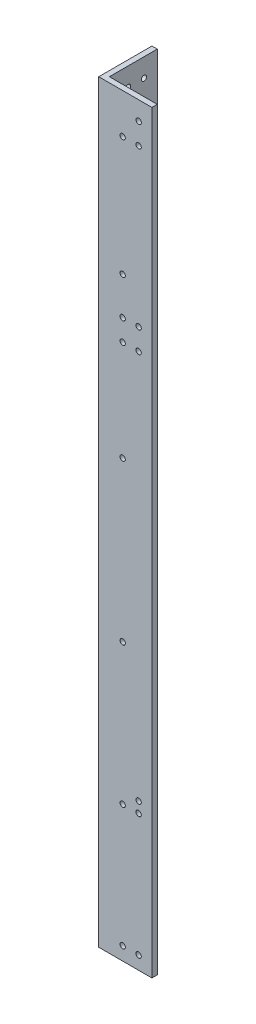
SolidWorks part; units mm, degrees
ref_plane "Front Plane" through (0, 0, 0) normal (0, 0, 1) x (1, 0, 0)
ref_plane "Top Plane" through (0, 0, 0) normal (0, 1, 0) x (1, 0, 0)
ref_plane "Right Plane" through (0, 0, 0) normal (1, 0, 0) x (0, 0, -1)
sketch "Sketch2" plane through (0, 0, 0) normal (0, 1, 0) x (1, 0, 0)
  line L0 (0, 31.75) -> (3.175, 31.75)
  line L1 (3.175, 31.75) -> (3.175, 3.175)
  line L2 (3.175, 3.175) -> (31.75, 3.175)
  line L3 (31.75, 3.175) -> (31.75, 0)
  line L4 (31.75, 0) -> (0, 0)
  line L5 (0, 0) -> (0, 31.75)
  point P9 (1.5875, 31.75)
  point P10 (31.75, 1.5875)
  dimension "D4" = 3.175
  dimension "D1" = 31.75
  dimension "D2" = 31.75
  dimension "D3" = 3.175
extrude "Boss-Extrude1" add sketch "Sketch2" along normal blind 450
sketch "LeftSideHoles-Sketch3" plane through (0, 0, 0) normal (0, 0, 1) x (1, 0, 0)
  line L0 (0, 0) -> (31.75, 0) construction
  line L1 (0, 450) -> (31.75, 450) construction
  line L3 (0, 450) -> (0, 0) construction
  circle A0 centre (14.2875, 81.1125) radius 1.5875
  circle A1 centre (23.8125, 81.1125) radius 1.5875
  circle A3 centre (23.8125, 87.4625) radius 1.5875
  circle A5 centre (14.2875, 426.1875) radius 1.5875
  circle A6 centre (23.8125, 438.8875) radius 1.5875
  circle A7 centre (23.8125, 426.1875) radius 1.5875
  circle A10 centre (14.2875, 332.6026) radius 1.5875
  circle A11 centre (23.8125, 332.6026) radius 1.5875
  circle A12 centre (14.2875, 319.9026) radius 1.5875
  circle A13 centre (23.8125, 319.9026) radius 1.5875
  circle A14 centre (14.2875, 7.9375) radius 1.5875
  circle A15 centre (23.8125, 7.9375) radius 1.5875
  circle A16 centre (14.2875, 165) radius 1.5875
  circle A17 centre (14.2875, 260) radius 1.5875
  circle A18 centre (14.2875, 355) radius 1.5875
  point P24 (15.875, 0)
  dimension "D4" = 3.175
  dimension "D1" = 81.1125
  dimension "D2" = 14.2875
  dimension "D10" = 7.9375
  dimension "D7" = 12.7
  dimension "D3" = 9.525
  dimension "D11" = 332.6026
  dimension "D12" = 165
  dimension "D13" = 95
  dimension "D14" = 95
  dimension "D5" = 6.35
  dimension "D6" = 12.7
  dimension "D8" = 11.1125
sketch "BackSideHoles-Sketch4" plane through (0, 0, 0) normal (-1, 0, 0) x (0, 0, 1)
  line L0 (-31.75, 450) -> (0, 450) construction
  line L2 (0, 450) -> (0, 0) construction
  line L3 (-31.75, 0) -> (0, 0) construction
  circle A0 centre (-23.8125, 81.1125) radius 1.5875
  circle A2 centre (-23.8125, 87.4625) radius 1.5875
  circle A3 centre (-14.2875, 87.4625) radius 1.5875
  circle A4 centre (-23.8125, 438.8875) radius 1.5875
  circle A5 centre (-14.2875, 438.8875) radius 1.5875
  circle A6 centre (-23.8125, 426.1875) radius 1.5875
  circle A10 centre (-23.8125, 332.6026) radius 1.5875
  circle A11 centre (-14.2875, 332.6026) radius 1.5875
  circle A12 centre (-23.8125, 326.2526) radius 1.5875
  circle A13 centre (-14.2875, 326.2526) radius 1.5875
  circle A14 centre (-14.2875, 165) radius 1.5875
  circle A15 centre (-14.2875, 260) radius 1.5875
  circle A16 centre (-14.2875, 355) radius 1.5875
  circle A17 centre (-23.8125, 7.9375) radius 1.5875
  circle A18 centre (-14.2875, 7.9375) radius 1.5875
  dimension "D4" = 3.175
  dimension "D2" = 14.2875
  dimension "D7" = 12.7
  dimension "D5" = 6.35
  dimension "D6" = 11.1125
  dimension "D8" = 6.35
  dimension "D1" = 332.6026
  dimension "D10" = 165
  dimension "D11" = 95
  dimension "D12" = 95
  dimension "D13" = 7.9375
  dimension "D3" = 81.1125
  dimension "D9" = 9.525
extrude "LeftSideHoles-Cut-Extrude1" cut sketch "LeftSideHoles-Sketch3" against normal blind 3.175
extrude "BackSideHoles-Cut-Extrude2" cut sketch "BackSideHoles-Sketch4" against normal blind 3.175
equation "\"RailThickness\"= .125in'Spec"
equation "\"VSWidth\"= 1.25in'Spec"
equation "\"VSHeight\"= 1.25in'Spec"
equation "\"VSLength\"= 450mm"
equation "\"HoleOffsetFromEdge\"= \"RailThickness\" * 2.5"
equation "\"HoleOffsetFromSide\"= \"RailThickness\" * 3.5"
equation "\"LegHeight\"= 70mm'Space needed for PSU/Stepper/Electronics"
equation "\"VSBottomSideRailHoleY1FromBottomOfLowerRail\"= \"V1 BottomOfLowerRail\" + \"HoleOffsetFromSide\"'Equals 70.1125"
equation "\"VSSideRailHoleX1FromSide\"= \"HoleOffsetFromSide\" + \"RailThickness\""
equation "\"FasteningHoleDiameter\"= .125in"
equation "\"VSBottomSideRailHoleY2FromY1\"= \"LowerRailHeight\" - \"HoleOffsetFromSide\" - \"HoleOffsetFromEdge\"'Equals 6.35"
equation "\"VSTopSideRailHoleY1FromEdge\"= \"HoleOffsetFromEdge\" + \"RailThickness\""
equation "\"D4@LeftSideHoles-Sketch3\"=\"FasteningHoleDiameter\""
equation "\"D1@LeftSideHoles-Sketch3\"=\"VSBottomSideRailHoleY1FromBottomOfLowerRail\""
equation "\"D2@LeftSideHoles-Sketch3\"=\"VSSideRailHoleX1FromSide\""
equation "\"D1@Boss-Extrude1\"=\"VSLength\""
equation "\"D4@BackSideHoles-Sketch4\" = \"FasteningHoleDiameter\""
equation "\"VSMidSideRailHoleY1FromV8TopOfMidSideRail\"= \"V8 ToTopOfMidSideRail\" - \"HoleOffsetFromEdge\"'Equals 308.2875"
equation "\"LowerRailHeight\"= 1.00in"
equation "\"D1@Sketch2\"=\"VSHeight\""
equation "\"D2@Sketch2\"=\"VSWidth\""
equation "\"MidBackRailHeight\"= 1.00in"
equation "\"VSMidBackRailHoleY1FromV7TopOfMidBackRail\"= \"V7 ToTopOfMidBackRail\" - \"HoleOffsetFromSide\"'Equals 308.2875"
equation "\"TopRailHeight\"= 1.25in"
equation "\"MidSideRailHeight\"= 1.25in"
equation "\"D10@LeftSideHoles-Sketch3\"=\"HoleOffsetFromEdge\""
equation "\"VSMidBackRailHoleY2FromY1\"= \"MidBackRailHeight\" - \"HoleOffsetFromSide\" - \"HoleOffsetFromEdge\"'Equals 6.35"
equation "\"VSMidSideRailHoleY2FromY1\"= \"MidSideRailHeight\" - \"HoleOffsetFromSide\" - \"HoleOffsetFromEdge\"'Equals 12.7"
equation "\"D7@LeftSideHoles-Sketch3\"=\"VSMidSideRailHoleY2FromY1\""
equation "\"D8@BackSideHoles-Sketch4\"=\"VSMidBackRailHoleY2FromY1\""
equation "\"D6@BackSideHoles-Sketch4\"=\"VSTopSideRailHoleY1FromEdge\""
equation "\"VSTopSideRailHoleY2FromY1\"= \"TopRailHeight\" - \"VSTopSideRailHoleY1FromEdge\" - \"HoleOffsetFromEdge\"'Equals 12.7"
equation "\"D7@BackSideHoles-Sketch4\"=\"VSTopSideRailHoleY2FromY1\""
equation "\"VSBottomSideRailHoleX2FromX1\"= \"VSWidth\" - \"VSSideRailHoleX1FromSide\" - \"HoleOffsetFromEdge\""
equation "\"D3@LeftSideHoles-Sketch3\"=\"VSBottomSideRailHoleX2FromX1\""
equation "\"V1 BottomOfLowerRail\"= \"LegHeight\""
equation "\"StepperShaftLength\"= 24mm'Pulley will be attached to the end"
equation "\"ZAxisLeadScrewLength\"= 200mm"
equation "\"LM8UUHeight\"= 24mm'Spec"
equation "\"V2 ToBedAtTopOfZAxis\"= \"V1 BottomOfLowerRail\" + \"StepperShaftLength\" + \"ZAxisLeadScrewLength\" - \"LM8UUHeight\" / 2"
equation "\"HotEndToTopOfXAxisGB\"= 63.315144mm'Measured from the100.Should be 63.315144"
equation "\"TopOfGBToBottomOfLinearRail\"= \"LinearGBWidth\" / 2 + \"LinearRailWidth\" / 2"
equation "\"LinearGBWidth\"= 27mm'Spec"
equation "\"V5 ToBottomOfXAxisLinearRail\"= \"V4 ToTopOfBuildPlate/HotEndTip\" + \"HotEndToTopOfXAxisGB\" - \"TopOfGBToBottomOfLinearRail\""
equation "\"LinearRailWidth\"= 12mm'Spec"
equation "\"V6 ToBottomOfGantryPulley\"= \"V5 ToBottomOfXAxisLinearRail\" - \"DistanceFromGABTopToLowerPulley\""
equation "\"GABUpperHeight\"= 6mm"
equation "\"GABMidWallHeight\"= 28mm'Must equal 28 or changes alignment"
equation "\"20TGT2PulleyWidth\"= 8.7mm'The STL of the Pulley in the diagram is a bit larger"
equation "\"GABMidShortRiserHeight\"= \"GABMidWallHeight\" / 2 - \"20TGT2PulleyWidth\"'Equals 5.3"
equation "\"GABRiserBossOffset\"= 0.8mm'Aligns Pulleys"
equation "\"DistanceFromGABTopToLowerPulley\"= \"GABUpperHeight\" + \"GABMidWallHeight\" - \"GABMidShortRiserHeight\" + \"GABRiserBossOffset\" / 2"
equation "\"V7 ToTopOfMidBackRail\"= \"V6 ToBottomOfGantryPulley\" + \"StepperShaftLength\""
equation "\"D1@BackSideHoles-Sketch4\" = \"VSMidBackRailHoleY1FromV7TopOfMidBackRail\""
equation "\"D11@LeftSideHoles-Sketch3\"=\"VSMidSideRailHoleY1FromV8TopOfMidSideRail\""
equation "\"V4 ToTopOfBuildPlate/HotEndTip\"= \"V2 ToBedAtTopOfZAxis\" + \"BedToBuildPlateStandoffLength\" + \"BuildPlateHeight\""
equation "\"BedToBuildPlateStandoffLength\"= 15mm"
equation "\"BuildPlateHeight\"= 8mm'Spec"
equation "\"V8 ToTopOfMidSideRail\"= \"V7 ToTopOfMidBackRail\" - \"RailThickness\""
equation "\"VSEnclosureOffsets\"= ( \"VSLength\" - \"LegHeight\" ) / 4"
equation "\"D12@LeftSideHoles-Sketch3\"=\"LegHeight\" + \"VSEnclosureOffsets\""
equation "\"D13@LeftSideHoles-Sketch3\"=\"VSEnclosureOffsets\""
equation "\"D14@LeftSideHoles-Sketch3\"=\"VSEnclosureOffsets\""
equation "\"D10@BackSideHoles-Sketch4\"=\"LegHeight\" + \"VSEnclosureOffsets\""
equation "\"D11@BackSideHoles-Sketch4\"=\"VSEnclosureOffsets\""
equation "\"D12@BackSideHoles-Sketch4\"=\"VSEnclosureOffsets\""
equation "\"D13@BackSideHoles-Sketch4\"=\"HoleOffsetFromEdge\""
equation "\"D5@BackSideHoles-Sketch4\"=\"VSBottomSideRailHoleY2FromY1\""
equation "\"D3@BackSideHoles-Sketch4\"=\"VSBottomSideRailHoleY1FromBottomOfLowerRail\""
equation "\"D2@BackSideHoles-Sketch4\"=\"VSSideRailHoleX1FromSide\""
equation "\"D5@LeftSideHoles-Sketch3\"=\"VSBottomSideRailHoleY2FromY1\""
equation "\"D6@LeftSideHoles-Sketch3\"=\"VSTopSideRailHoleY2FromY1\""
equation "\"D8@LeftSideHoles-Sketch3\"=\"VSTopSideRailHoleY1FromEdge\""
